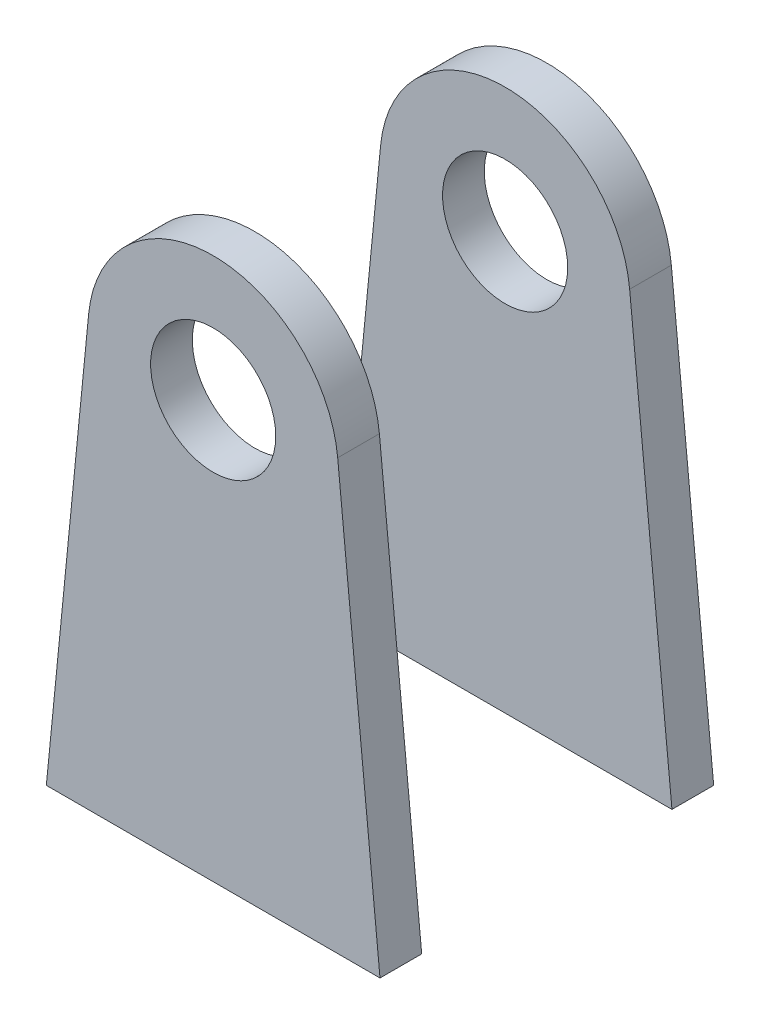
SolidWorks part; units mm, degrees
ref_plane "Front Plane" through (0, 0, 0) normal (0, 0, 1) x (1, 0, 0)
ref_plane "Top Plane" through (0, 0, 0) normal (0, 1, 0) x (1, 0, 0)
ref_plane "Right Plane" through (0, 0, 0) normal (1, 0, 0) x (0, 0, -1)
sketch "Sketch1" plane through (0, 0, 0) normal (0, 0, 1) x (1, 0, 0)
  line L0 (0, 0) -> (0, -31.75) construction
  line L1 (-9.4791, 0.9341) -> (-12.7, -31.75)
  line L2 (9.4791, 0.9341) -> (12.7, -31.75)
  line L3 (-12.7, -31.75) -> (12.7, -31.75)
  circle A0 centre (0, 0) radius 4.7625
  circle A1 centre (0, 0) radius 9.525
  dimension "D1" = 25.4
  dimension "D2" = 9.525
  dimension "D4" = 19.05
  dimension "D3" = 31.75
extrude "Boss-Extrude1" add sketch "Sketch1" against normal blind 3.175 from offset 12.7 contours A0 A1 | L0 A1 L1 | A1 L0 L2 region at (-6.8581, -6.2155, 0) region at (5.9988, -19.7917, 0) region at (-5.9988, -19.7917, 0)
extrude "Boss-Extrude2" add sketch "Sketch1<4>" along normal blind 3.175 from offset 12.7 separate body contours A0 A1 | A1 L0 L2 | L0 A1 L1 region at (-6.8581, -6.2155, 0) region at (5.9988, -19.7917, 0) region at (-5.9988, -19.7917, 0) offset against normal yes
sketch "Sketch1<4>" plane through (0, 0, 0) normal (0, 0, 1) x (1, 0, 0) same geometry as "Sketch1"
